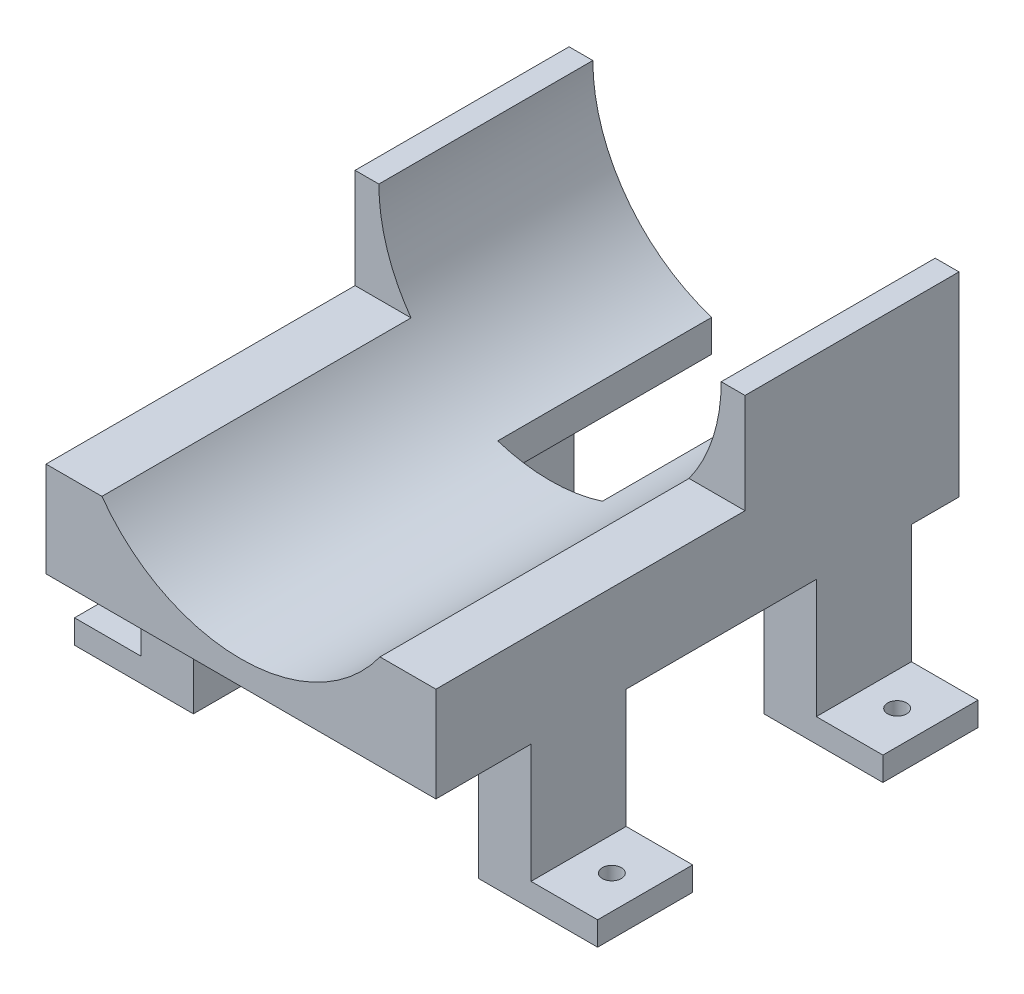
SolidWorks part; units mm, degrees
ref_plane "前基準面" through (0, 0, 0) normal (0, 0, 1) x (1, 0, 0)
ref_plane "上基準面" through (0, 0, 0) normal (0, 1, 0) x (1, 0, 0)
ref_plane "右基準面" through (0, 0, 0) normal (1, 0, 0) x (0, 0, -1)
sketch "草圖1" plane through (0, 0, 0) normal (0, 0, 1) x (1, 0, 0)
  line L0 (-41, 0) -> (41, 0) construction
  line L1 (-41, 0) -> (-41, -41)
  line L2 (-41, -41) -> (41, -41)
  line L3 (41, -41) -> (41, 0)
  circle A0 centre (0, 0) radius 36
  arc A1 (41, 0) -> (-41, 0) centre (0, 0) ccw
  circle A2 centre (0, 0) radius 41 construction
  dimension "D1" = 72
  dimension "D2" = 5
extrude "填料-伸長1" add sketch "草圖1" along normal blind 90
sketch "草圖2" plane through (0, 0, 0) normal (0, 0, 1) x (1, 0, 0)
  line L0 (0, 42.9462) -> (0, -46.3268) construction
  line L2 (11, -34.2783) -> (-11, -34.2783)
  line L3 (11, -34.2783) -> (11, -41)
  line L4 (11, -41) -> (-11, -41)
  line L5 (-11, -34.2783) -> (-11, -41)
  line L6 (0, -41) -> (0, -34.2783) construction
  line L7 (11, -37.6391) -> (-11, -37.6391) construction
  circle A0 centre (0, 0) radius 36 construction
  circle A1 centre (0, 0) radius 41 construction
  point P3 (0, -37.6391)
  dimension "D1" = 22
extrude "除料-伸長1" cut sketch "草圖2" along normal blind 45
sketch "草圖3" plane through (0, 0, 0) normal (1, 0, 0) x (0, 0, -1)
  line L1 (0, 41) -> (-90, 41)
  line L2 (0, 41) -> (0, 0)
  line L3 (0, 0) -> (-45, 0)
  line L4 (-90, 41) -> (-90, -21)
  line L5 (-90, -41) -> (-90, 0) construction
  line L8 (-90, -21) -> (-45, -21)
  line L9 (-45, -21) -> (-45, 0)
  dimension "D3" = 45
  dimension "D1" = 21
  dimension "D2" = 90
extrude "除料-伸長2" cut sketch "草圖3" against normal through all both and the other way through all
sketch "草圖4" plane through (0, 0, 90) normal (0, 0, 1) x (1, 0, 0)
  line L0 (-47.0781, 0) -> (47.0781, 0) construction
  line L5 (-30, -71) -> (-30, -27.9464)
  line L6 (0, 52.2232) -> (0, -44.5988) construction
  line L10 (30, -71) -> (30, -27.9464)
  line L12 (29.2404, -21) -> (41, -21) construction
  line L13 (-41, -66) -> (-55, -66)
  line L15 (-30, -71) -> (-55, -71)
  line L16 (-55, -66) -> (-55, -71)
  line L17 (41, -66) -> (55, -66)
  line L19 (30, -71) -> (55, -71)
  line L20 (55, -66) -> (55, -71)
  line L21 (35.2136, -21) -> (41, -21)
  line L22 (-41, -21) -> (-29.2404, -21) construction
  line L23 (-41, -21) -> (-35.2136, -21)
  line L24 (-41, -21) -> (-41, -66)
  line L25 (41, -21) -> (41, -66)
  line L26 (-41, -41) -> (41, -41) construction
  arc A0 (-35.2136, -21) -> (35.2136, -21) centre (0, 0) ccw construction
  arc A3 (41, 0) -> (-41, 0) centre (0, 0) ccw construction
  arc A4 (-35.2136, -21) -> (-30, -27.9464) centre (0, 0) ccw
  arc A5 (30, -27.9464) -> (35.2136, -21) centre (0, 0) ccw
  dimension "D5" = 82
  dimension "D1" = 5
  dimension "D2" = 30
  dimension "D3" = 60
  dimension "D4" = 25
extrude "填料-伸長3" add sketch "草圖4" against normal blind 20
sketch "草圖5" plane through (0, -66, 0) normal (0, 1, 0) x (1, 0, 0)
  line L0 (-55, -80) -> (55, -80) construction
  line L1 (-55, -70) -> (-55, -90) construction
  line L2 (55, -70) -> (55, -90) construction
  line L3 (0, 0) -> (0, -88.7499) construction
  line L4 (-41, -90) -> (-55, -90) construction
  circle A0 centre (-48, -80) radius 2
  circle A1 centre (48, -80) radius 2
  point P17 (-48, -90)
  dimension "D1" = 4
extrude "除料-伸長3" cut sketch "草圖5" against normal through all
pattern_linear "直線複製排列1" count 2 spacing 60 along (0, 0, -1) of "填料-伸長3", "除料-伸長3"
sketch "草圖6" plane through (0, 0, 90) normal (0, 0, 1) x (1, 0, 0)
  line L0 (-29.2404, -21) -> (-41, -21)
  line L1 (-41, -21) -> (-41, -41)
  line L2 (-41, -21) -> (-41, -66) construction
  line L3 (-41, -41) -> (41, -41)
  line L4 (41, -66) -> (41, -21) construction
  line L5 (41, -41) -> (41, -21)
  line L6 (41, -21) -> (29.2404, -21)
  line L7 (-30, -41) -> (30, -41) construction
  circle A0 centre (0, 0) radius 36 construction
  arc A1 (-29.2404, -21) -> (29.2404, -21) centre (0, 0) ccw
  point P16 (0, -36)
  dimension "D1" = 15
  dimension "D2" = 21
extrude "填料-伸長4" add sketch "草圖6" along normal blind 20
